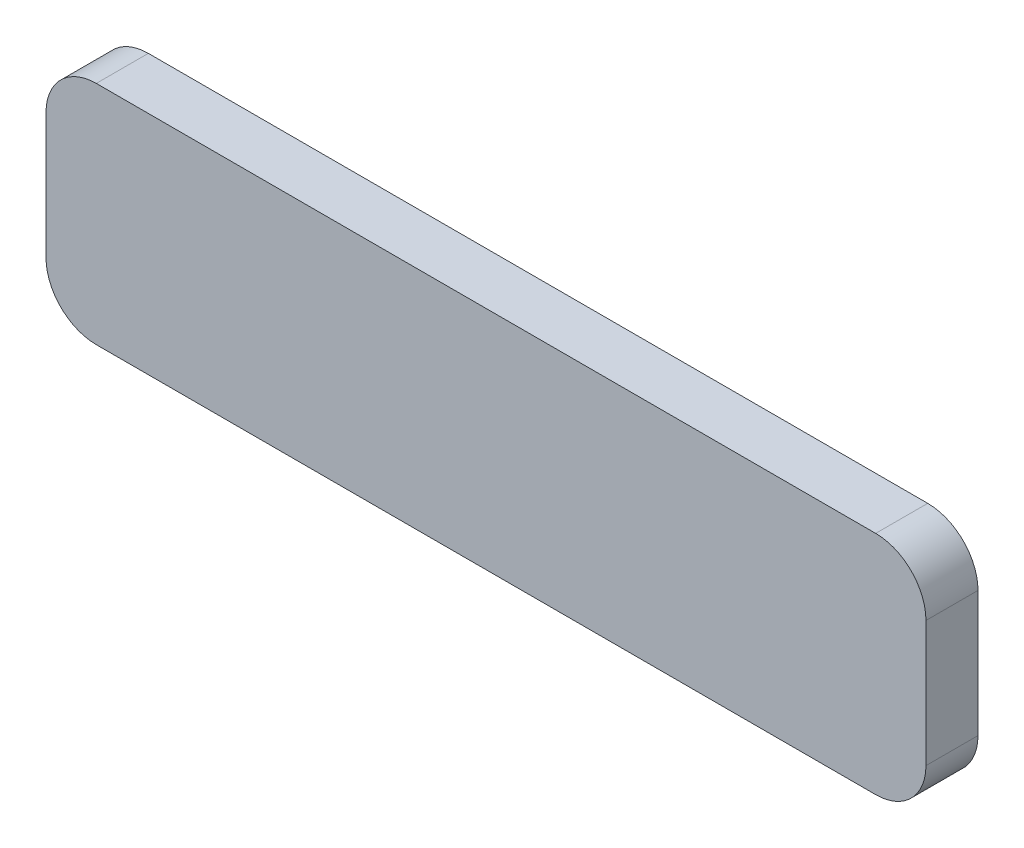
SolidWorks part; units mm, degrees
ref_plane "Front Plane" through (0, 0, 0) normal (0, 0, 1) x (1, 0, 0)
ref_plane "Top Plane" through (0, 0, 0) normal (0, 1, 0) x (1, 0, 0)
ref_plane "Right Plane" through (0, 0, 0) normal (1, 0, 0) x (0, 0, -1)
sketch "Sketch1" plane through (0, 0, 0) normal (0, 0, 1) x (1, 0, 0)
  line L1 (-44.45, -11.43) -> (44.45, -11.43)
  line L2 (-44.45, -11.43) -> (-44.45, 11.43)
  line L3 (-44.45, 11.43) -> (44.45, 11.43)
  line L4 (44.45, -11.43) -> (44.45, 11.43)
  line L5 (-44.45, -11.43) -> (44.45, 11.43) construction
  line L6 (-44.45, 11.43) -> (44.45, -11.43) construction
  point P0 (0, 0)
  dimension "D1" = 88.9
  dimension "D2" = 22.86
extrude "Boss-Extrude1" add sketch "Sketch1" along normal blind 5.2578
fillet "Fillet1" radius 5.08 1 edges at (-44.45, 11.43, 2.6289) type face fillet first side face at (0, 11.43, 2.6289) second side face at (-44.45, 0, 2.6289)
fillet "Fillet2" radius 5.08 1 edges at (44.45, 11.43, 2.6289) type face fillet first side face at (2.54, 11.43, 2.6289) second side face at (44.45, 0, 2.6289)
fillet "Fillet3" radius 5.08 1 edges at (44.45, -11.43, 2.6289) type face fillet first side face at (44.45, -2.54, 2.6289) second side face at (0, -11.43, 2.6289)
fillet "Fillet4" radius 5.08 1 edges at (-44.45, -11.43, 2.6289) type face fillet first side face at (-44.45, -2.54, 2.6289) second side face at (-2.54, -11.43, 2.6289)
equation "\"Acrylic\"=\"Acrylic@Bumper.assembly\""
equation "\"D1@Boss-Extrude1\"=\"Acrylic\""
equation "\"D1@Sketch1\" = \"BumperWidth@Bumper_short.assembly\"+1"
